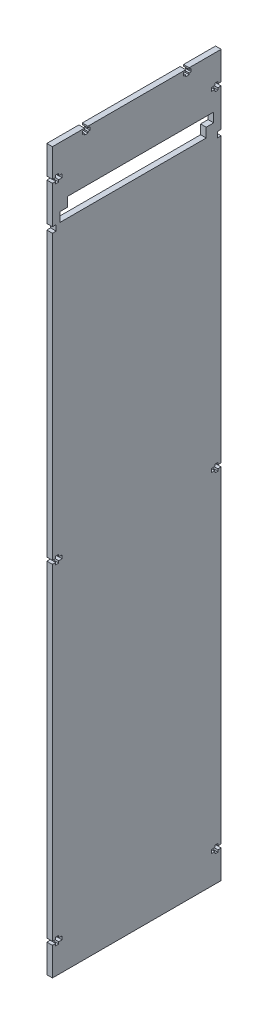
SolidWorks part; units mm, degrees
ref_plane "Front Plane" through (0, 0, 0) normal (0, 0, 1) x (1, 0, 0)
ref_plane "Top Plane" through (0, 0, 0) normal (0, 1, 0) x (1, 0, 0)
ref_plane "Right Plane" through (0, 0, 0) normal (1, 0, 0) x (0, 0, -1)
sketch "Sketch1" plane through (0, 0, 0) normal (0, 1, 0) x (1, 0, 0)
  line L1 (0, 0) -> (4.7625, 0)
  line L2 (0, 0) -> (0, 142.875)
  line L3 (0, 142.875) -> (4.7625, 142.875)
  line L4 (4.7625, 0) -> (4.7625, 142.875)
  dimension "D1" = 142.875
  dimension "D2" = 4.7625
extrude "Boss-Extrude1" add sketch "Sketch1" along normal blind 609.6
sketch "Sketch12" plane through (0, 0, 0) normal (-1, 0, 0) x (0, 0, 1)
  line L0 (0, 609.6) -> (0, 0) construction
  line L1 (-6.35, 550.8625) -> (-130.175, 550.8625)
  line L2 (-6.35, 550.8625) -> (-6.35, 558.8)
  line L3 (-6.35, 558.8) -> (-130.175, 558.8)
  line L4 (-130.175, 550.8625) -> (-130.175, 558.8)
  line L5 (-142.875, 609.6) -> (0, 609.6) construction
  dimension "D1" = 123.825
  dimension "D2" = 6.35
  dimension "D3" = 50.8
  dimension "D4" = 7.9375
extrude "Cut-Extrude7" cut sketch "Sketch12" against normal through all
sketch "Sketch13" plane through (0, 0, 0) normal (-1, 0, 0) x (0, 0, 1)
  line L0 (-6.35, 558.8) -> (-130.175, 558.8) construction
  line L1 (-12.7, 558.8) -> (-136.525, 558.8)
  line L2 (-12.7, 558.8) -> (-12.7, 566.7375)
  line L3 (-12.7, 566.7375) -> (-136.525, 566.7375)
  line L4 (-136.525, 558.8) -> (-136.525, 566.7375)
  line L5 (-142.875, 609.6) -> (-142.875, 0) construction
  point P6 (-136.525, 562.7688)
  dimension "D1" = 123.825
  dimension "D2" = 7.9375
  dimension "D3" = 6.35
extrude "Cut-Extrude8" cut sketch "Sketch13" against normal through all
sketch "Sketch14" plane through (0, 0, 0) normal (-1, 0, 0) x (0, 0, 1)
  line L0 (-6.35, 550.8625) -> (-6.35, 558.8) construction
  line L1 (-12.7, 558.8) -> (-12.7, 566.7375) construction
  line L2 (-6.35, 558.8) -> (-12.7, 558.8) construction
  line L3 (-130.175, 550.8625) -> (-6.35, 550.8625) construction
  line L4 (-130.175, 558.8) -> (-130.175, 550.8625) construction
  line L5 (-136.525, 558.8) -> (-130.175, 558.8) construction
  line L6 (-136.525, 566.7375) -> (-136.525, 558.8) construction
  line L7 (-12.7, 566.7375) -> (-136.525, 566.7375) construction
  line L8 (-6.35, 550.8625) -> (-6.35, 558.8)
  line L9 (-12.7, 558.8) -> (-12.7, 566.7375)
  line L10 (-6.35, 558.8) -> (-12.7, 558.8)
  line L11 (-130.175, 550.8625) -> (-6.35, 550.8625)
  line L12 (-130.175, 558.8) -> (-130.175, 550.8625)
  line L13 (-136.525, 558.8) -> (-130.175, 558.8)
  line L14 (-136.525, 566.7375) -> (-136.525, 558.8)
  line L15 (-12.7, 566.7375) -> (-136.525, 566.7375)
  line L16 (-130.302, 550.7355) -> (-6.223, 550.7355)
  line L17 (-6.223, 550.7355) -> (-6.223, 558.927)
  line L18 (-6.223, 558.927) -> (-12.573, 558.927)
  line L19 (-12.573, 558.927) -> (-12.573, 566.8645)
  line L20 (-12.573, 566.8645) -> (-136.652, 566.8645)
  line L21 (-136.652, 566.8645) -> (-136.652, 558.673)
  line L22 (-136.652, 558.673) -> (-130.302, 558.673)
  line L23 (-130.302, 558.673) -> (-130.302, 550.7355)
  dimension "D1" = 0.127
extrude "Cut-Extrude9" [suppressed] cut sketch "Sketch14" against normal through all
sketch "Sketch15" plane through (0, 0, 0) normal (-1, 0, 0) x (0, 0, 1)
  line L0 (0, 550.8625) -> (-142.875, 550.8625) construction
  line L1 (0, 609.6) -> (0, 0) construction
  line L2 (-142.875, 609.6) -> (-142.875, 0) construction
  line L4 (0, 550.8625) -> (-3.175, 550.8625)
  line L5 (0, 550.8625) -> (0, 546.1)
  line L6 (0, 546.1) -> (-3.175, 546.1)
  line L7 (-3.175, 550.8625) -> (-3.175, 546.1)
  line L8 (-142.875, 550.8625) -> (-139.7, 550.8625)
  line L9 (-142.875, 550.8625) -> (-142.875, 546.1)
  line L10 (-142.875, 546.1) -> (-139.7, 546.1)
  line L11 (-139.7, 550.8625) -> (-139.7, 546.1)
  dimension "D1" = 3.175
  dimension "D2" = 4.7625
extrude "Cut-Extrude10" cut sketch "Sketch15" against normal through all
sketch "Sketch16" plane through (0, 0, 0) normal (-1, 0, 0) x (0, 0, 1)
  line L0 (0, 25.4) -> (-142.875, 25.4) construction
  line L1 (0, 546.1) -> (0, 0) construction
  line L2 (-142.875, 546.1) -> (-142.875, 0) construction
  line L3 (-71.4375, 0) -> (-71.4375, 609.6) construction
  line L4 (-142.875, 0) -> (0, 0) construction
  line L5 (-142.875, 609.6) -> (0, 609.6) construction
  line L6 (-2.794, 23.9395) -> (-2.794, 22.1996)
  line L7 (-8.128, 23.9395) -> (-5.334, 23.9395)
  line L8 (-8.128, 23.9395) -> (-8.128, 26.8605)
  line L9 (-8.128, 26.8605) -> (-5.334, 26.8605)
  line L10 (0, 23.9395) -> (0, 26.8605)
  line L11 (-8.128, 23.9395) -> (0, 26.8605) construction
  line L12 (-8.128, 26.8605) -> (0, 23.9395) construction
  line L13 (-2.794, 28.6004) -> (-5.334, 28.6004)
  line L14 (-2.794, 28.6004) -> (-2.794, 26.8605)
  line L15 (-2.794, 22.1996) -> (-5.334, 22.1996)
  line L16 (-5.334, 28.6004) -> (-5.334, 26.8605)
  line L17 (-2.794, 28.6004) -> (-5.334, 22.1996) construction
  line L18 (-2.794, 22.1996) -> (-5.334, 28.6004) construction
  line L19 (-2.794, 23.9395) -> (0, 23.9395)
  line L20 (-5.334, 23.9395) -> (-5.334, 22.1996)
  line L21 (-2.794, 26.8605) -> (0, 26.8605)
  line L22 (-134.747, 26.8605) -> (-137.541, 26.8605)
  line L23 (-134.747, 23.9395) -> (-134.747, 26.8605)
  line L24 (-134.747, 23.9395) -> (-137.541, 23.9395)
  line L25 (-137.541, 23.9395) -> (-137.541, 22.1996)
  line L26 (-140.081, 22.1996) -> (-137.541, 22.1996)
  line L27 (-140.081, 23.9395) -> (-140.081, 22.1996)
  line L28 (-140.081, 23.9395) -> (-142.875, 23.9395)
  line L29 (-142.875, 23.9395) -> (-142.875, 26.8605)
  line L30 (-140.081, 26.8605) -> (-142.875, 26.8605)
  line L31 (-140.081, 28.6004) -> (-140.081, 26.8605)
  line L32 (-140.081, 28.6004) -> (-137.541, 28.6004)
  line L33 (-137.541, 28.6004) -> (-137.541, 26.8605)
  line L34 (-134.747, 306.2605) -> (-137.541, 306.2605)
  line L35 (-134.747, 303.3395) -> (-134.747, 306.2605)
  line L36 (-134.747, 303.3395) -> (-137.541, 303.3395)
  line L37 (-137.541, 303.3395) -> (-137.541, 301.5996)
  line L38 (-140.081, 301.5996) -> (-137.541, 301.5996)
  line L39 (-140.081, 303.3395) -> (-140.081, 301.5996)
  line L40 (-140.081, 303.3395) -> (-142.875, 303.3395)
  line L41 (-142.875, 303.3395) -> (-142.875, 306.2605)
  line L42 (-140.081, 306.2605) -> (-142.875, 306.2605)
  line L43 (-140.081, 308.0004) -> (-140.081, 306.2605)
  line L44 (-140.081, 308.0004) -> (-137.541, 308.0004)
  line L45 (-137.541, 308.0004) -> (-137.541, 306.2605)
  line L46 (-2.794, 303.3395) -> (-2.794, 301.5996)
  line L47 (-8.128, 303.3395) -> (-5.334, 303.3395)
  line L48 (-8.128, 303.3395) -> (-8.128, 306.2605)
  line L49 (-8.128, 306.2605) -> (-5.334, 306.2605)
  line L50 (0, 303.3395) -> (0, 306.2605)
  line L51 (-2.794, 308.0004) -> (-5.334, 308.0004)
  line L52 (-2.794, 308.0004) -> (-2.794, 306.2605)
  line L53 (-2.794, 301.5996) -> (-5.334, 301.5996)
  line L54 (-5.334, 308.0004) -> (-5.334, 306.2605)
  line L55 (-2.794, 303.3395) -> (0, 303.3395)
  line L56 (-5.334, 303.3395) -> (-5.334, 301.5996)
  line L57 (-2.794, 306.2605) -> (0, 306.2605)
  line L58 (0, 304.8) -> (-142.875, 304.8) construction
  line L59 (-8.128, 303.3395) -> (0, 306.2605) construction
  line L60 (-8.128, 306.2605) -> (0, 303.3395) construction
  line L61 (-2.794, 308.0004) -> (-5.334, 301.5996) construction
  line L62 (-2.794, 301.5996) -> (-5.334, 308.0004) construction
  line L63 (-134.747, 585.6605) -> (-137.541, 585.6605)
  line L64 (-134.747, 582.7395) -> (-134.747, 585.6605)
  line L65 (-134.747, 582.7395) -> (-137.541, 582.7395)
  line L66 (-137.541, 582.7395) -> (-137.541, 580.9996)
  line L67 (-140.081, 580.9996) -> (-137.541, 580.9996)
  line L68 (-140.081, 582.7395) -> (-140.081, 580.9996)
  line L69 (-140.081, 582.7395) -> (-142.875, 582.7395)
  line L70 (-142.875, 582.7395) -> (-142.875, 585.6605)
  line L71 (-140.081, 585.6605) -> (-142.875, 585.6605)
  line L72 (-140.081, 587.4004) -> (-140.081, 585.6605)
  line L73 (-140.081, 587.4004) -> (-137.541, 587.4004)
  line L74 (-137.541, 587.4004) -> (-137.541, 585.6605)
  line L75 (-2.794, 582.7395) -> (-2.794, 580.9996)
  line L76 (-8.128, 582.7395) -> (-5.334, 582.7395)
  line L77 (-8.128, 582.7395) -> (-8.128, 585.6605)
  line L78 (-8.128, 585.6605) -> (-5.334, 585.6605)
  line L79 (0, 582.7395) -> (0, 585.6605)
  line L80 (-2.794, 587.4004) -> (-5.334, 587.4004)
  line L81 (-2.794, 587.4004) -> (-2.794, 585.6605)
  line L82 (-2.794, 580.9996) -> (-5.334, 580.9996)
  line L83 (-5.334, 587.4004) -> (-5.334, 585.6605)
  line L84 (-2.794, 582.7395) -> (0, 582.7395)
  line L85 (-5.334, 582.7395) -> (-5.334, 580.9996)
  line L86 (-2.794, 585.6605) -> (0, 585.6605)
  line L87 (0, 584.2) -> (-142.875, 584.2) construction
  line L88 (-8.128, 582.7395) -> (0, 585.6605) construction
  line L89 (-8.128, 585.6605) -> (0, 582.7395) construction
  line L90 (-2.794, 587.4004) -> (-5.334, 580.9996) construction
  line L91 (-2.794, 580.9996) -> (-5.334, 587.4004) construction
  point P12 (-4.064, 25.4)
  point P17 (-4.064, 25.4)
  point P42 (-4.064, 304.8)
  point P47 (-4.064, 304.8)
  point P70 (-4.064, 584.2)
  point P75 (-4.064, 584.2)
  dimension "D1" = 8.128
  dimension "D2" = 2.921
  dimension "D3" = 25.4
  dimension "D4" = 2.54
  dimension "D5" = 6.4008
  dimension "D6" = 3
extrude "Cut-Extrude11" cut sketch "Sketch16" against normal through all
sketch "Sketch17" plane through (0, 0, 0) normal (-1, 0, 0) x (0, 0, 1)
  line L0 (-142.875, 609.6) -> (0, 609.6) construction
  line L1 (-28.575, 0) -> (-28.575, 609.6) construction
  line L2 (-142.875, 0) -> (0, 0) construction
  line L3 (0, 609.6) -> (0, 585.6605) construction
  line L4 (-71.4375, 0) -> (-71.4375, 609.6) construction
  line L5 (-27.1145, 604.52) -> (-30.0355, 604.52)
  line L6 (-27.1145, 604.52) -> (-27.1145, 605.79)
  line L7 (-27.1145, 609.6) -> (-30.0355, 609.6)
  line L8 (-30.0355, 604.52) -> (-30.0355, 605.79)
  line L9 (-27.1145, 604.52) -> (-30.0355, 609.6) construction
  line L10 (-27.1145, 609.6) -> (-30.0355, 604.52) construction
  line L11 (-25.3746, 605.79) -> (-27.1145, 605.79)
  line L12 (-25.3746, 605.79) -> (-25.3746, 608.33)
  line L13 (-25.3746, 608.33) -> (-27.1145, 608.33)
  line L14 (-31.7754, 605.79) -> (-31.7754, 608.33)
  line L15 (-25.3746, 605.79) -> (-31.7754, 608.33) construction
  line L16 (-25.3746, 608.33) -> (-31.7754, 605.79) construction
  line L17 (-27.1145, 608.33) -> (-27.1145, 609.6)
  line L18 (-30.0355, 608.33) -> (-31.7754, 608.33)
  line L19 (-30.0355, 608.33) -> (-30.0355, 609.6)
  line L20 (-30.0355, 605.79) -> (-31.7754, 605.79)
  line L21 (-115.7605, 604.52) -> (-112.8395, 604.52)
  line L22 (-115.7605, 604.52) -> (-115.7605, 605.79)
  line L23 (-117.5004, 605.79) -> (-115.7605, 605.79)
  line L24 (-117.5004, 605.79) -> (-117.5004, 608.33)
  line L25 (-117.5004, 608.33) -> (-115.7605, 608.33)
  line L26 (-115.7605, 608.33) -> (-115.7605, 609.6)
  line L27 (-115.7605, 609.6) -> (-112.8395, 609.6)
  line L28 (-112.8395, 608.33) -> (-112.8395, 609.6)
  line L29 (-112.8395, 608.33) -> (-111.0996, 608.33)
  line L30 (-111.0996, 605.79) -> (-111.0996, 608.33)
  line L31 (-112.8395, 605.79) -> (-111.0996, 605.79)
  line L32 (-112.8395, 604.52) -> (-112.8395, 605.79)
  point P8 (-28.575, 607.06)
  point P13 (-28.575, 607.06)
  dimension "D1" = 28.575
  dimension "D2" = 5.08
  dimension "D3" = 2.921
  dimension "D4" = 2.54
  dimension "D5" = 6.4008
extrude "Cut-Extrude12" cut sketch "Sketch17" against normal through all
